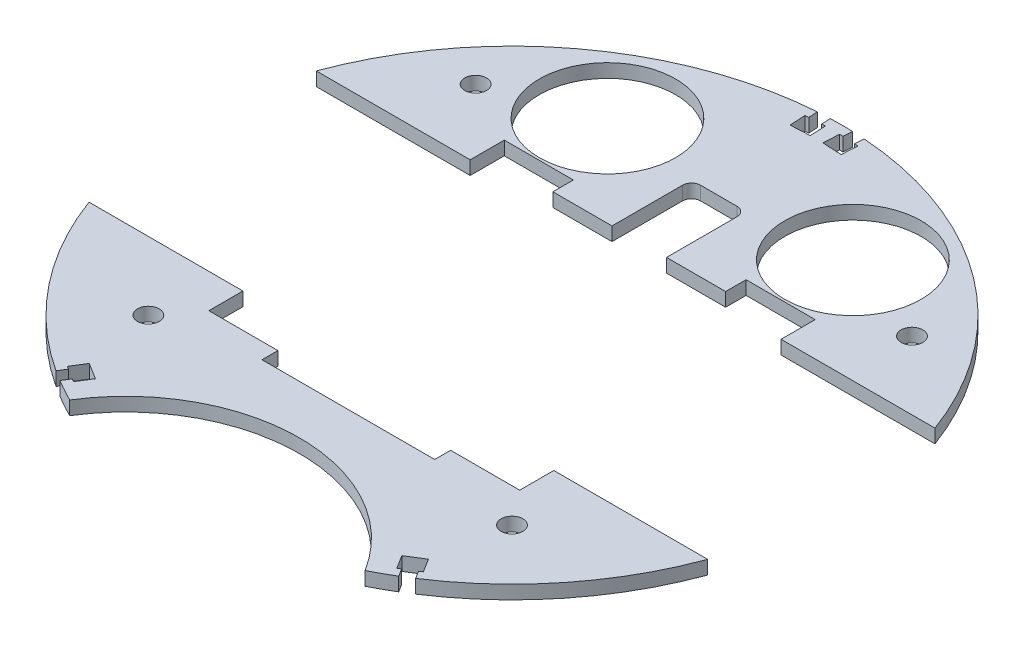
SolidWorks part; units mm, degrees
material "ABS"
ref_plane "Front Plane" through (0, 0, 0) normal (0, 0, 1) x (1, 0, 0)
ref_plane "Top Plane" through (0, 0, 0) normal (0, 1, 0) x (1, 0, 0)
ref_plane "Right Plane" through (0, 0, 0) normal (1, 0, 0) x (0, 0, -1)
sketch "Sketch1" plane through (0, 0, 0) normal (0, 1, 0) x (1, 0, 0)
  line L0 (0, -85) -> (-32.4891, -64.8129) construction
  line L1 (0, -85) -> (0, 0) construction
  arc A0 (32.4891, -64.8129) -> (-32.4891, -64.8129) centre (0, 0) ccw
  arc A1 (32.4891, -64.8129) -> (-32.4891, -64.8129) centre (0, -85) ccw
  dimension "D1" = 145
  dimension "D2" = 76.5
  dimension "D3" = 85
extrude "Boss-Extrude1" add sketch "Sketch1" along normal blind 3
sketch "solenoid placement" plane through (0, 3, 0) normal (0, 1, 0) x (1, 0, 0)
  line L4 (-19, -36) -> (19, -36)
  line L5 (-19, 28) -> (-19, -36)
  line L10 (19, 28) -> (-19, 28)
  line L11 (19, -36) -> (19, 28)
  line L12 (-19, -36) -> (19, -36)
  line L13 (-19, 28) -> (-19, -36)
  line L14 (19, 28) -> (-19, 28)
  line L15 (19, -36) -> (19, 28)
  dimension "D1" = 0
extrude "Cut-Extrude1" cut sketch "solenoid placement" against normal through all
sketch "Sketch7" plane through (0, 3, 0) normal (0, 1, 0) x (1, 0, 0)
  circle A3 centre (27, 48) radius 15
  circle A4 centre (27, 48) radius 15
  circle A5 centre (-27, 48) radius 15
  circle A6 centre (-27, 48) radius 15
  dimension "D1" = 0
  dimension "D2" = 0
extrude "Cut-Extrude6" cut sketch "Sketch7" against normal through all
sketch "Sketch8" plane through (0, 3, 0) normal (0, 1, 0) x (1, 0, 0)
  circle A1 centre (40, -40) radius 2.4
  circle A2 centre (40, -40) radius 2.4
  circle A3 centre (-40, -40) radius 2.4
  circle A4 centre (-40, -40) radius 2.4
  circle A5 centre (48, 40) radius 2.4
  circle A6 centre (48, 40) radius 2.4
  circle A7 centre (-48, 40) radius 2.4
  circle A8 centre (-48, 40) radius 2.4
  dimension "D1" = 0
  dimension "D2" = 0
  dimension "D3" = 0
  dimension "D4" = 0
extrude "Cut-Extrude7" cut sketch "Sketch8" against normal through all
sketch "Sketch3" plane through (0, 3, 0) normal (0, 1, 0) x (1, 0, 0)
  line L1 (-34.2, -32.5) -> (-22.2, -32.5)
  line L2 (-34.2, 25) -> (-68.0533, 25)
  line L3 (-34.2, 32.5) -> (-22.2, 32.5)
  line L4 (-22.2, -32.5) -> (-22.2, 32.5) construction
  line L8 (0, 0) -> (0, 72.5) construction
  line L17 (-34.2, -32.5) -> (-34.2, -25)
  line L18 (-34.2, -25) -> (-68.0533, -25)
  line L19 (-34.2, 25) -> (-34.2, 32.5)
  line L21 (-22.2, 32.5) -> (-19, 32.5)
  line L22 (-22.2, 32.5) -> (-22.2, -32.5) construction
  line L23 (-22.2, -32.5) -> (-19, -32.5)
  line L24 (-19, 32.5) -> (-19, -32.5)
  line L25 (22.2, 32.5) -> (22.2, -32.5) construction
  line L26 (22.2, -32.5) -> (22.2, 32.5) construction
  line L27 (19, 32.5) -> (19, -32.5)
  line L28 (22.2, -32.5) -> (19, -32.5)
  line L29 (22.2, 32.5) -> (19, 32.5)
  line L30 (34.2, 25) -> (34.2, 32.5)
  line L31 (34.2, -25) -> (68.0533, -25)
  line L32 (34.2, -32.5) -> (34.2, -25)
  line L33 (34.2, 32.5) -> (22.2, 32.5)
  line L34 (34.2, 25) -> (68.0533, 25)
  line L35 (34.2, -32.5) -> (22.2, -32.5)
  line L36 (-19, 28) -> (-19, -36) construction
  arc A0 (32.4891, -64.8129) -> (-32.4891, -64.8129) centre (0, 0) ccw construction
  arc A2 (68.0533, 25) -> (68.0533, -25) centre (0, 0) cw
  arc A3 (-68.0533, 25) -> (-68.0533, -25) centre (0, 0) ccw
  point P31 (-34.2, -32.5)
  dimension "D1" = 50
extrude "Cut-Extrude3" cut sketch "Sketch3" against normal through all
sketch "Sketch9" plane through (0, 3, 0) normal (0, 1, 0) x (1, 0, 0)
  line L0 (6, 43.5) -> (6, 28)
  line L1 (-6, 43.5) -> (-6, 28)
  line L2 (19, 28) -> (-19, 28) construction
  line L8 (-6, 28) -> (6, 28)
  line L10 (4, 45.5) -> (-4, 45.5)
  arc A0 (-6, 43.5) -> (-4, 45.5) centre (-4, 43.5) cw
  arc A1 (6, 43.5) -> (4, 45.5) centre (4, 43.5) ccw
  point P5 (0, 28)
  point P6 (0, 28)
  point P16 (-6, 45.5)
  point P19 (6, 45.5)
  dimension "D3" = 2
  dimension "D2" = 12
  dimension "D1" = 17.5
extrude "Cut-Extrude8" cut sketch "Sketch9" against normal through all
sketch "Sketch10" plane through (0, 3, 0) normal (0, 1, 0) x (1, 0, 0)
  line L0 (0, 0) -> (0, 72.5) construction
  line L1 (0, 0) -> (3.7944, 72.4006) construction
  line L2 (1.3844, 67.0194) -> (5.6286, 66.797)
  line L3 (1.3844, 67.0194) -> (1.5676, 70.5146)
  line L4 (5.6286, 66.797) -> (5.8118, 70.2922)
  line L5 (1.5676, 70.5146) -> (2.3415, 70.474)
  line L6 (2.3415, 70.474) -> (2.4462, 72.4713)
  line L7 (2.4462, 72.4713) -> (5.1425, 72.33)
  line L8 (5.1425, 72.33) -> (5.0378, 70.3327)
  line L9 (5.0378, 70.3327) -> (5.8118, 70.2922)
  line L10 (-5.0378, 70.3327) -> (-5.8118, 70.2922)
  line L11 (-5.1425, 72.33) -> (-5.0378, 70.3327)
  line L12 (-2.4462, 72.4713) -> (-5.1425, 72.33)
  line L13 (-2.3415, 70.474) -> (-2.4462, 72.4713)
  line L14 (-1.5676, 70.5146) -> (-2.3415, 70.474)
  line L15 (-5.6286, 66.797) -> (-5.8118, 70.2922)
  line L16 (-1.3844, 67.0194) -> (-1.5676, 70.5146)
  line L17 (-1.3844, 67.0194) -> (-5.6286, 66.797)
  line L18 (37.3067, -55.6931) -> (33.7025, -57.9453)
  line L19 (37.3067, -55.6931) -> (39.1614, -58.6613)
  line L20 (33.7025, -57.9453) -> (35.5572, -60.9135)
  line L21 (39.1614, -58.6613) -> (38.5042, -59.072)
  line L22 (38.5042, -59.072) -> (39.564, -60.7681)
  line L23 (39.564, -60.7681) -> (37.2743, -62.1989)
  line L24 (37.2743, -62.1989) -> (36.2144, -60.5028)
  line L25 (36.2144, -60.5028) -> (35.5572, -60.9135)
  line L26 (0, 0) -> (38.4191, -61.4835) construction
  line L27 (0, 0) -> (0, -85) construction
  line L28 (-33.7025, -57.9453) -> (-37.3067, -55.6931)
  line L29 (-33.7025, -57.9453) -> (-35.5572, -60.9135)
  line L30 (-37.3067, -55.6931) -> (-39.1614, -58.6613)
  line L31 (-35.5572, -60.9135) -> (-36.2144, -60.5028)
  line L32 (-36.2144, -60.5028) -> (-37.2743, -62.1989)
  line L33 (-37.2743, -62.1989) -> (-39.564, -60.7681)
  line L34 (-39.564, -60.7681) -> (-38.5042, -59.072)
  line L35 (-38.5042, -59.072) -> (-39.1614, -58.6613)
  line L36 (0, 0) -> (-38.4191, -61.4835) construction
  arc A1 (68.0533, 25) -> (-68.0533, 25) centre (0, 0) ccw construction
  point P1 (3.5065, 66.9082)
  point P15 (3.7944, 72.4006)
  point P36 (0, 0)
  point P49 (0, 0)
  dimension "D1" = 3.5
  dimension "D2" = 4.25
  dimension "D3" = 3
  dimension "D4" = 2.7
  dimension "D5" = 2
  dimension "D7" = 32
  dimension "D9" = 32
  dimension "D6" = 2
  dimension "D8" = 2
extrude "Cut-Extrude9" cut sketch "Sketch10" against normal through all
sketch "Sketch11" plane through (0, 3, 0) normal (0, 1, 0) x (1, 0, 0)
  line L4 (4, 48.5) -> (-4, 48.5)
  line L5 (7.1569, 48.5) -> (-7.1569, 48.5)
  line L10 (-8.4675, 63.6441) -> (-1.2274, 64.0235)
  line L11 (-8.8077, 70.1352) -> (-8.4675, 63.6441)
  line L12 (-6.4702, 63.7487) -> (-0.1047, 64.0823)
  line L13 (-8.6309, 66.7627) -> (-8.5721, 65.6413)
  line L17 (8.4675, 63.6441) -> (8.8077, 70.1352)
  line L18 (1.2274, 64.0235) -> (8.4675, 63.6441)
  line L19 (8.5721, 65.6413) -> (8.6309, 66.7627)
  line L20 (0.1047, 64.0823) -> (6.4702, 63.7487)
  arc A0 (-9.1412, 50.25) -> (-7.1569, 48.5) centre (-7.1569, 50.5) ccw
  arc A1 (9.1412, 50.25) -> (7.1569, 48.5) centre (7.1569, 50.5) cw
  arc A2 (18.004, 63.5907) -> (17.5082, 67.2585) centre (17.0044, 65.323) ccw
  arc A3 (10.9431, 68.6331) -> (8.6309, 66.7627) centre (10.6282, 66.658) ccw
  arc A4 (8.5721, 65.6413) -> (6.4702, 63.7487) centre (6.5749, 65.746) cw
  arc A5 (-0.1047, 64.0823) -> (0.1047, 64.0823) centre (0, 62.0851) cw
  arc A6 (-6.4702, 63.7487) -> (-8.5721, 65.6413) centre (-6.5749, 65.746) cw
  arc A7 (-10.9431, 68.6331) -> (-8.6309, 66.7627) centre (-10.6282, 66.658) cw
  arc A8 (-17.5082, 67.2585) -> (-18.004, 63.5907) centre (-17.0044, 65.323) ccw
  circle A9 centre (-27, 48) radius 18
  arc A10 (-9.1412, 50.25) -> (-18.004, 63.5907) centre (-27, 48) ccw
  circle A12 centre (27, 48) radius 18
  arc A13 (18.004, 63.5907) -> (9.1412, 50.25) centre (27, 48) ccw
  arc A15 (-4.9291, 69.325) -> (-65.2373, 23.9655) centre (0, 0) ccw
  arc A16 (-10.9431, 68.6331) -> (-17.5082, 67.2585) centre (0, 0) ccw
  arc A17 (17.5082, 67.2585) -> (10.9431, 68.6331) centre (0, 0) ccw
  dimension "D5" = 2
  dimension "D1" = 3
  dimension "D2" = 3
  dimension "D3" = 3
  dimension "D4" = 3
  dimension "D6" = 3
  dimension "D7" = 3
extrude "Cut-Extrude10" [suppressed] cut sketch "Sketch11" against normal through all
equation "\"smallPulleyTeeth\"= 15"
equation "\"largePulleyTeeth\"= 30"
equation "\"eighthThick\"= 3.0mm"
equation "\"sixteenthThick\"= 1.7mm"
equation "\"quarterThick\"=6.0mm"
equation "\"OD\"= 145mm"
equation "\"puckAngle\"= 60.5deg"
equation "\"D1@Sketch1\"=\"OD\""
equation "\"puckDiam\"= 76.5mm"
equation "\"D2@Sketch1\"=\"puckDiam\""
equation "\"D1@Boss-Extrude1\"=\"eighthThick\""
equation "\"axlePress\"= 5.9mm"
equation "\"press\"= 0.2mm"
equation "\"wheelClear\"= 0.3mm"
equation "\"10-32clear\"= 4.8mm"
equation "\"6-32clear\"= 3.3mm"
equation "\"8-32clear\"= 4.0mm"
equation "\"4-40clear\"= 3.0mm"
equation "\"wheelHeight\"= 22mm"
equation "\"wheelWell\"= 65mm"
equation "\"puckDist\"= 85mm"
equation "\"D3@Sketch1\"=\"puckDist\""
equation "\"scoopFillet\"= 5mm"
equation "\"10-32tap\"= 4.45mm"
equation "\"ledSmall\"= 3.1mm"
equation "\"ledLarge\"= 4.2mm"
equation "\"ledLength\"= 4.2mm"
equation "\"4-40close\"= 2.7mm"
equation "\"4-40nutThick\"= 2.2mm"
equation "\"4-40nutWidth\"= 6.2mm"
equation "\"4-40insertHeight\"= 3.5mm"
equation "\"4-40insert\"= 4.25mm"
equation "\"D1@Sketch10\"=\"4-40insertHeight\""
equation "\"D2@Sketch10\"=\"4-40insert\""
equation "\"D4@Sketch10\"=\"4-40close\""
